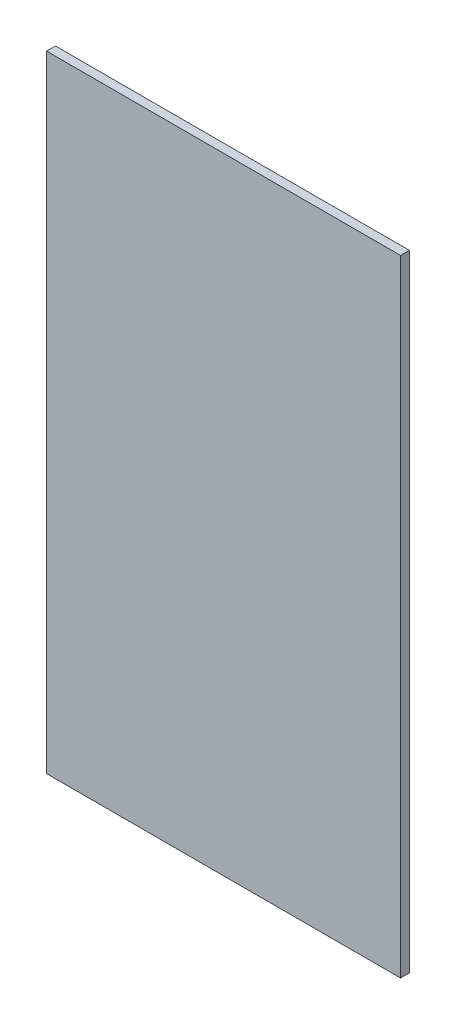
SolidWorks part; units mm, degrees
ref_plane "Front Plane" through (0, 0, 0) normal (1, 0, 0) x (0, 1, 0)
ref_plane "Top Plane" through (0, 0, 0) normal (0, 0, 1) x (0, 1, 0)
ref_plane "Right Plane" through (0, 0, 0) normal (0, 1, 0) x (-1, 0, 0)
sketch "Sketch1" plane through (0, 0, 0) normal (0, 0, 1) x (0, 1, 0)
  line L1 (-112.268, -63.5) -> (112.268, -63.5)
  line L2 (-112.268, -63.5) -> (-112.268, 63.5)
  line L3 (-112.268, 63.5) -> (112.268, 63.5)
  line L4 (112.268, -63.5) -> (112.268, 63.5)
  line L5 (-112.268, -63.5) -> (112.268, 63.5) construction
  line L6 (-112.268, 63.5) -> (112.268, -63.5) construction
  point P1 (0, 0)
  dimension "D1" = 224.536
  dimension "D2" = 127
extrude "Boss-Extrude1" add sketch "Sketch1" along normal blind 3.175
